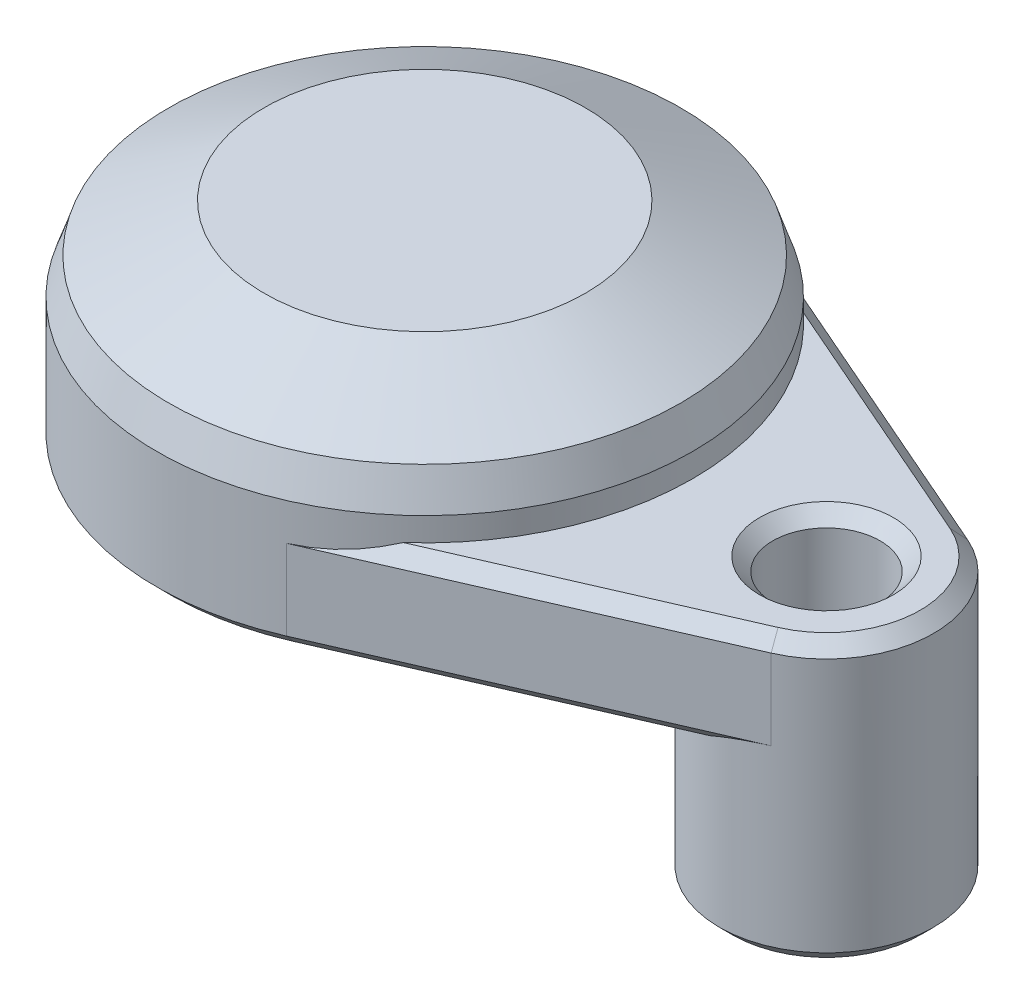
SolidWorks part; units mm, degrees
ref_plane "前视基准面" through (0, 0, 0) normal (0, 0, 1) x (1, 0, 0)
ref_plane "上视基准面" through (0, 0, 0) normal (0, 1, 0) x (1, 0, 0)
ref_plane "右视基准面" through (0, 0, 0) normal (1, 0, 0) x (0, 0, -1)
other "Configuration Table"
sketch "草图1" plane through (0, 0, 0) normal (0, 1, 0) x (1, 0, 0)
  line L0 (0, 0) -> (7.5, 0) construction
  line L1 (2, -4.5826) -> (8.3, -1.833)
  line L2 (8.3, 1.833) -> (2, 4.5826)
  arc A0 (2, 4.5826) -> (2, -4.5826) centre (0, 0) ccw
  arc A1 (8.3, -1.833) -> (8.3, 1.833) centre (7.5, 0) ccw
  dimension "D1" = 10
  dimension "D3" = 4
  dimension "D2" = 7.5
extrude "凸台-拉伸1" add sketch "草图1" along normal blind 2
sketch "草图2" plane through (0, 0, 0) normal (0, 1, 0) x (1, 0, 0)
  arc A0 (8.3, -1.833) -> (8.3, 1.833) centre (7.5, 0) ccw construction
  arc A1 (8.3, -1.833) -> (8.3, 1.833) centre (7.5, 0) ccw construction
  circle A3 centre (7.5, 0) radius 2
extrude "凸台-拉伸2" add sketch "草图2" against normal blind 3.25
sketch "草图3" plane through (0, 0, 0) normal (0, 1, 0) x (1, 0, 0)
  circle A0 centre (0, 0) radius 1.5
  arc A1 (8.3, -1.833) -> (8.3, 1.833) centre (7.5, 0) ccw construction
  arc A2 (8.3, -1.833) -> (8.3, 1.833) centre (7.5, 0) ccw construction
  circle A3 centre (7.5, 0) radius 1
  dimension "D1" = 3
  dimension "D2" = 2
extrude "切除-拉伸1" cut sketch "草图3" against normal up to surface (3.25 mm away) from surface up to face at (7.5, -3.25, 2) starting at face at (3.7, 2, 0)
sketch "草图4" plane through (0, 0, 0) normal (0, 0, 1) x (1, 0, 0)
  line L0 (0, -1000) -> (0, 49000) construction
  line L1 (0, 2) -> (5, 2)
  line L2 (1.5, 2) -> (-1.5, 2) construction
  line L3 (2, 2) -> (8.3, 2) construction
  line L4 (5, 2) -> (5, 3)
  line L5 (5, 3) -> (3, 4)
  line L6 (3, 4) -> (0, 4)
  line L7 (0, 4) -> (0, 2)
  dimension "D1" = 5
  dimension "D2" = 3
  dimension "D3" = 1
  dimension "D4" = 2
revolve "旋转1" add sketch "草图4" angle 360 about L0
chamfer "倒角1" distance 0.25 angle 45 4 edges at (5, 3, 0) (5.15, 0, -3.2078) (5.15, 0, 3.2078) (-5, 0, 0) first distance on face at (3, 4, 0) first distance on face at (0, 0, 1.5)
chamfer "倒角2" distance 0.25 angle 45 7 edges at (0, 0, 1.5) (7.5, -3.25, 1) (7.5, -3.25, 2) (5.15, 2, 3.2078) (5.15, 2, -3.2078) (9.5, 2, 0) (7.5, 2, 1)
